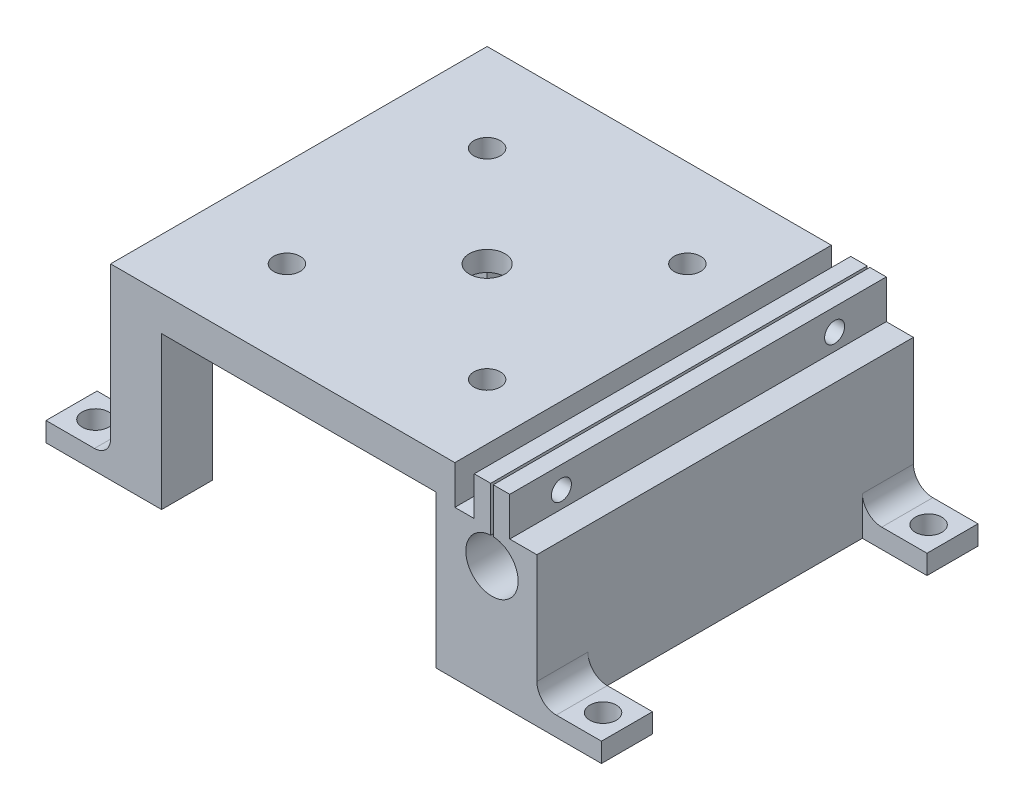
SolidWorks part; units mm, degrees
ref_plane "Спереди" through (0, 0, 0) normal (0, 0, 1) x (1, 0, 0)
ref_plane "Сверху" through (0, 0, 0) normal (0, 1, 0) x (1, 0, 0)
ref_plane "Справа" through (0, 0, 0) normal (1, 0, 0) x (0, 0, -1)
other "Configuration Table"
sketch "Sketch1" plane through (0, 0, 0) normal (0, 1, 0) x (1, 0, 0)
  line L0 (-33, 29.15) -> (-3.85, 29.15) construction
  line L1 (-33, -29.15) -> (33, -29.15)
  line L2 (-33, -29.15) -> (-33, 29.15)
  line L3 (-33, 29.15) -> (33, 29.15)
  line L4 (33, -29.15) -> (33, 29.15)
  line L5 (-33, -29.15) -> (33, 29.15) construction
  line L6 (-33, 29.15) -> (33, -29.15) construction
  line L7 (-3.85, 29.15) -> (-3.85, 0) construction
  circle A1 centre (-3.85, 0) radius 2.75
  point P0 (0, 0)
  dimension "D5" = 5.5
  dimension "D1" = 66
  dimension "D2" = 58.3
  dimension "D3" = 29.15
  dimension "D4" = 29.15
extrude "Boss-Extrude1" add sketch "Sketch1" along normal blind 29
sketch "Sketch3" plane through (0, 29, 0) normal (0, 1, 0) x (1, 0, 0)
  line L0 (-33, 21.25) -> (-33, -21.25)
  line L1 (-33, 29.15) -> (-33, -29.15) construction
  line L2 (-33, -21.25) -> (-25.1, -21.25)
  line L3 (-25.1, -21.25) -> (-25.1, -29.15)
  line L4 (-33, -29.15) -> (33, -29.15) construction
  line L5 (-25.1, -29.15) -> (17.4, -29.15)
  line L6 (17.4, -29.15) -> (17.4, 29.15)
  line L7 (33, 29.15) -> (-33, 29.15) construction
  line L8 (17.4, 29.15) -> (-25.1, 29.15)
  line L9 (-25.1, 29.15) -> (-25.1, 21.25)
  line L10 (-25.1, 21.25) -> (-33, 21.25)
  dimension "D1" = 7.9
  dimension "D2" = 7.9
  dimension "D3" = 7.9
  dimension "D4" = 7.9
  dimension "D5" = 42.5
extrude "Cut-Extrude1" cut sketch "Sketch3" along normal blind 23.6 from surface starting at face at (0, 0, 0)
sketch "Sketch4" plane through (0, 23.6, 0) normal (0, -1, 0) x (1, 0, 0)
  circle A0 centre (-3.85, 0) radius 11.5
  dimension "D1" = 23
extrude "Cut-Extrude2" cut sketch "Sketch4" against normal blind 2.3
sketch "Sketch5" plane through (0, 29, 0) normal (0, 1, 0) x (1, 0, 0)
  line L0 (-3.85, 0) -> (-19.35, 0) construction
  line L1 (-3.85, 0) -> (-3.85, 15.5) construction
  line L2 (-19.35, 0) -> (-19.35, 15.5) construction
  line L3 (-19.35, 15.5) -> (-3.85, 15.5) construction
  circle A0 centre (-19.35, 15.5) radius 2.05
  circle A1 centre (11.65, 15.5) radius 2.05
  circle A2 centre (11.65, -15.5) radius 2.05
  circle A3 centre (-19.35, -15.5) radius 2.05
  dimension "D3" = 4.1
  dimension "D1" = 15.5
  dimension "D2" = 15.5
extrude "Cut-Extrude3" cut sketch "Sketch5" against normal up to next
sketch "Sketch6" plane through (0, 0, 0) normal (0, -1, 0) x (1, 0, 0)
  line L0 (-33, 29.15) -> (-33, 21.25)
  line L1 (-33, 29.15) -> (-43, 29.15)
  line L2 (-33, 21.25) -> (-43, 21.25)
  line L3 (-43, 29.15) -> (-43, 21.25)
  line L4 (-33, -21.25) -> (-33, -29.15)
  line L5 (-33, -21.25) -> (-43, -21.25)
  line L6 (-33, -29.15) -> (-43, -29.15)
  line L7 (-43, -21.25) -> (-43, -29.15)
  line L8 (33, 29.15) -> (33, 21.25)
  line L9 (33, 29.15) -> (43, 29.15)
  line L10 (33, 21.25) -> (43, 21.25)
  line L11 (43, 29.15) -> (43, 21.25)
  line L12 (33, 29.15) -> (33, -29.15) construction
  line L13 (33, -21.25) -> (33, -29.15)
  line L14 (33, -21.25) -> (43, -21.25)
  line L15 (33, -29.15) -> (43, -29.15)
  line L16 (43, -21.25) -> (43, -29.15)
  line L17 (-38, -21.25) -> (-38, -29.15) construction
  line L18 (-38, 29.15) -> (-38, 21.25) construction
  line L19 (38, 29.15) -> (38, 21.25) construction
  line L20 (38, -21.25) -> (38, -29.15) construction
  circle A0 centre (-39.3, -25.2) radius 2.05
  circle A1 centre (-39.3, 25.2) radius 2.05
  circle A2 centre (39.3, 25.2) radius 2.05
  circle A3 centre (39.3, -25.2) radius 2.05
  dimension "D9" = 4.1
  dimension "D10" = 3.7
  dimension "D1" = 10
  dimension "D2" = 7.9
  dimension "D3" = 10
  dimension "D4" = 10
  dimension "D5" = 10
  dimension "D6" = 7.9
  dimension "D7" = 7.9
  dimension "D8" = 7.9
  dimension "D11" = 3.7
  dimension "D12" = 3.7
  dimension "D13" = 3.7
  dimension "D14" = 3.7
extrude "Boss-Extrude2" add sketch "Sketch6" against normal blind 3
sketch "Sketch7" plane through (0, 0, -29.15) normal (0, 0, -1) x (-1, 0, 0)
  line L0 (-33, 7) -> (-33, 6)
  line L1 (-33, 29) -> (-33, 3) construction
  line L2 (-36, 3) -> (-37, 3)
  line L3 (-33, 3) -> (-43, 3) construction
  line L4 (33, 7) -> (33, 5.5)
  line L5 (33, 29) -> (33, 3) construction
  line L6 (43, 3) -> (33, 3) construction
  line L7 (35.5, 3) -> (37, 3)
  line L8 (-36, 3) -> (-33, 3)
  line L9 (-33, 3) -> (-33, 6)
  line L10 (-36, 3) -> (-33, 3)
  line L11 (-33, 3) -> (-33, 6)
  line L12 (-36, 3) -> (-36, 2.3913)
  line L13 (33, 5.5) -> (33, 3)
  line L14 (33, 3) -> (35.5, 3)
  arc A0 (-33, 6) -> (-36, 3) centre (-36, 6) cw
  arc A1 (35.5, 3) -> (33, 5.5) centre (35.5, 5.5) cw
  point P10 (-33, 3)
  point P20 (33, 3)
  line M8 (43, 3) -> (33, 3)
  line M9 (33, 3) -> (33, 29)
  line M11 (-33, 29) -> (-33, 3)
  line M12 (-33, 3) -> (-43, 3)
  dimension "D3" = 3
  dimension "D6" = 2.5
  dimension "D1" = 4
  dimension "D2" = 4
  dimension "D4" = 4
  dimension "D5" = 4
extrude "Boss-Extrude4" add sketch "Sketch7" against normal up to surface (7.9 mm away) contours A1 M8 M9 | A0 M11 M12 region at (33.6701, 3.6701, -29.15) region at (-33.5584, 3.5584, -29.15) up to face at (38, 1.5, -21.25)
extrude "Boss-Extrude5" add sketch "Sketch7<5>" along normal up to surface (-50.4 mm away) from surface contours A1 M8 M9 | A0 M11 M12 region at (33.6701, 3.6701, -29.15) region at (-33.5584, 3.5584, -29.15) up to face at (-33.7, 8.8667, 21.25) starting at face at (-1.2833, 9.7667, 29.15)
sketch "Sketch7<5>" plane through (0, 0, -29.15) normal (0, 0, -1) x (-1, 0, 0) same geometry as "Sketch7"
sketch "Sketch8" plane through (0, 0, 29.15) normal (0, 0, 1) x (1, 0, 0)
  line L0 (17.4, 0) -> (26.05, 0) construction
  line L1 (17.4, 0) -> (43, 0) construction
  line L2 (26.05, 0) -> (26.05, 18) construction
  line L4 (33, 29) -> (33, 6) construction
  circle A0 centre (26.05, 18) radius 4.05
  dimension "D3" = 8.1
  dimension "D1" = 8.65
  dimension "D2" = 18
  dimension "D4" = 6.95
extrude "Cut-Extrude4" cut sketch "Sketch8" along normal up to next from surface starting at face at (-1.0717, 9.1115, -29.15)
sketch "Sketch10" plane through (0, 0, -29.15) normal (0, 0, -1) x (-1, 0, 0)
  line L0 (-33, 29) -> (-28.8, 29) construction
  line L1 (-33, 29) -> (33, 29) construction
  line L2 (-28.8, 29) -> (-23.3, 29) construction
  line L3 (-26.05, 18) -> (-22, 18) construction
  line L4 (-17.4, 23.6) -> (-17.4, 0) construction
  line L5 (-23.3, 23) -> (-23.3, 25.6) construction
  line L6 (-23.3, 29) -> (-20.3, 29)
  line L7 (-23.3, 29) -> (-23.3, 23)
  line L8 (-23.3, 23) -> (-20.3, 23)
  line L9 (-20.3, 29) -> (-20.3, 23)
  line L10 (-33, 29) -> (-33, 6) construction
  line L11 (-28.8, 29) -> (-33, 29)
  line L12 (-28.8, 29) -> (-28.8, 23)
  line L13 (-28.8, 23) -> (-33, 23)
  line L14 (-33, 29) -> (-33, 23)
  line L15 (-23.3, 23) -> (-23.3, 28.2) construction
  line L16 (-23.3, 23) -> (-23.3, 25.6) construction
  line L17 (-23.3, 25.6) -> (-28.8, 25.6) construction
  line L19 (-26.05, 29) -> (-26.05, 23) construction
  line L20 (-26.05, 18) -> (-26.05, 29) construction
  line L21 (-26.25, 29) -> (-25.85, 29)
  line L22 (-26.25, 29) -> (-26.25, 21.4)
  line L23 (-26.25, 21.4) -> (-25.85, 21.4)
  line L24 (-25.85, 29) -> (-25.85, 21.4)
  circle A0 centre (-26.05, 18) radius 4.05 construction
  dimension "D8" = 0.2
  dimension "D1" = 9.7
  dimension "D2" = 3
  dimension "D3" = 5.5
  dimension "D4" = 6
  dimension "D5" = 2.9
  dimension "D6" = 2.6
  dimension "D7" = 4.2
  dimension "D9" = 0.2
  dimension "D10" = 2.55
  dimension "D11" = 2.55
  dimension "D12" = 3.4
extrude "Cut-Extrude5" cut sketch "Sketch10" against normal up to next
sketch "Sketch11" plane through (28.8, 0, 0) normal (1, 0, 0) x (0, 0, -1)
  line L0 (-29.15, 23) -> (-21.15, 23) construction
  line L1 (-29.15, 23) -> (29.15, 23) construction
  line L2 (-21.15, 23) -> (-21.15, 25.6) construction
  line L3 (0, 29) -> (0, 23) construction
  line L4 (-29.15, 29) -> (29.15, 29) construction
  circle A0 centre (-21.15, 25.6) radius 1.55
  circle A1 centre (21.15, 25.6) radius 1.55
  dimension "D3" = 3.1
  dimension "D1" = 8
  dimension "D2" = 2.6
extrude "Cut-Extrude6" cut sketch "Sketch11" against normal up to surface (5.5 mm away) up to face at (23.3, 26, 0)
